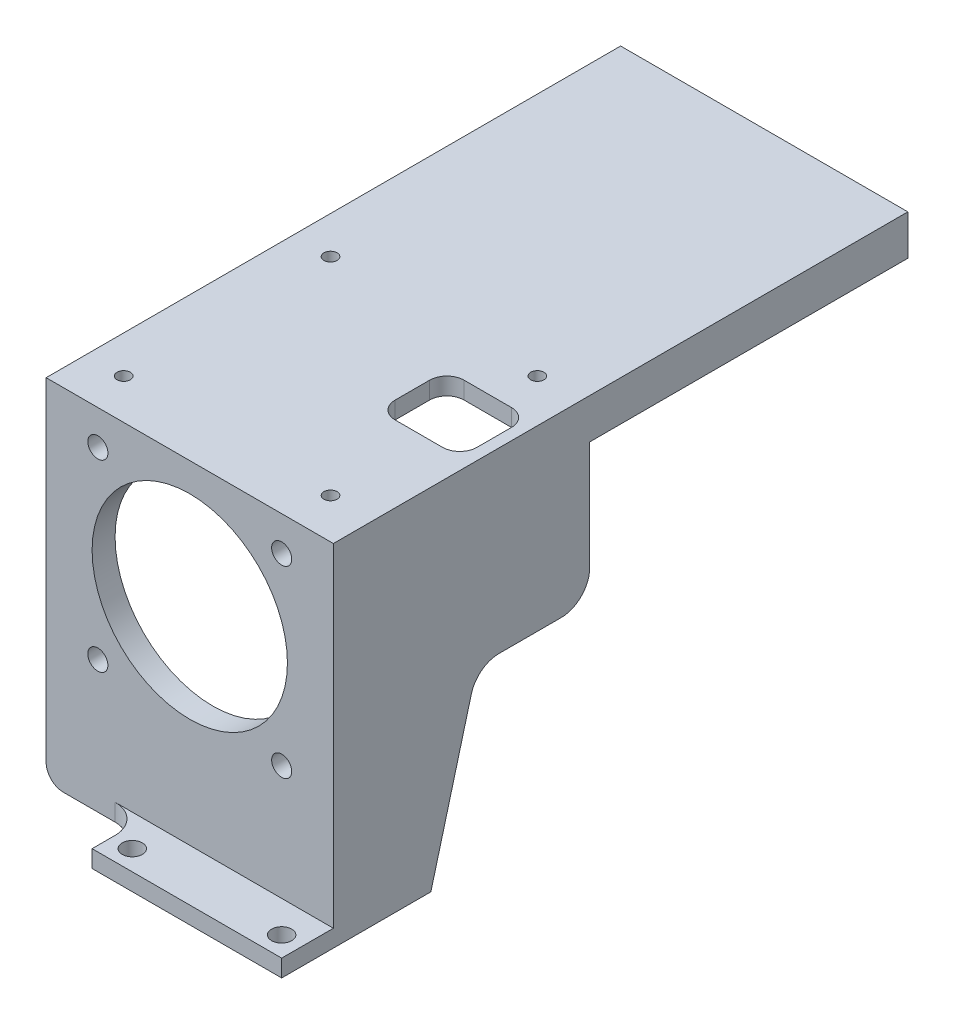
SolidWorks part; units mm, degrees
ref_plane "前视基准面" through (0, 0, 0) normal (0, 0, 1) x (1, 0, 0)
ref_plane "上视基准面" through (0, 0, 0) normal (0, 1, 0) x (1, 0, 0)
ref_plane "右视基准面" through (0, 0, 0) normal (1, 0, 0) x (0, 0, -1)
sketch "草图1" plane through (0, 0, 0) normal (0, 1, 0) x (1, 0, 0)
  line L1 (-16.5, -5) -> (16.5, -5)
  line L2 (-16.5, -5) -> (-16.5, 5)
  line L3 (-16.5, 5) -> (16.5, 5)
  line L4 (16.5, -5) -> (16.5, 5)
  line L5 (-16.5, -5) -> (16.5, 5) construction
  line L6 (-16.5, 5) -> (16.5, -5) construction
  point P0 (0, 0)
  dimension "D1" = 33
  dimension "D2" = 10
extrude "凸台-拉伸1" add sketch "草图1" along normal blind 3
sketch "草图2" plane through (0, 3, 0) normal (0, 1, 0) x (1, 0, 0)
  line L0 (16.5, -5) -> (16.5, 5) construction
  line L1 (-16.5, -5) -> (16.5, -5) construction
  line L2 (-16.5, 5) -> (-16.5, -5) construction
  point P0 (-13, -1.5)
  point P1 (13, -1.5)
  dimension "D1" = 3.5
  dimension "D2" = 3.5
  dimension "D3" = 3.5
  dimension "D4" = 3.5
sketch "草图3" plane through (0, 3, 0) normal (0, 1, 0) x (1, 0, 0)
  point P0 (-13, -1.5)
  point P3 (13, -1.5)
hole_wizard "孔1" positions "草图3" profile "草图4" legacy end condition through all
sketch "草图4" plane through (-13, 3, 1.5) normal (1, 0, 0) x (0, 0, 1)
  line L0 (0, 0) -> (0, 3)
  line L1 (0, 3) -> (1.75, 3)
  line L2 (1.75, 3) -> (1.75, 0)
  line L3 (1.75, 0) -> (0, 0)
  line L4 (0, 110) -> (0, -10) construction
  dimension "直径" = 3.5
  dimension "深度" = 3
sketch "草图5" plane through (0, 0, 0) normal (0, -1, 0) x (1, 0, 0)
  line L1 (-16.5, -5) -> (16.5, -5)
  line L2 (-16.5, -5) -> (-16.5, -8)
  line L3 (-16.5, -8) -> (16.5, -8)
  line L4 (16.5, -5) -> (16.5, -8)
  dimension "D1" = 33
  dimension "D2" = 3
extrude "凸台-拉伸2" add sketch "草图5" against normal blind 3
sketch "草图6" plane through (0, 3, 0) normal (0, 1, 0) x (1, 0, 0)
  line L0 (16.5, -5) -> (16.5, 8) construction
  line L1 (-16.5, 8) -> (16.5, 8)
  line L2 (-16.5, 8) -> (-16.5, 4)
  line L3 (-16.5, 4) -> (16.5, 4)
  line L4 (16.5, 8) -> (16.5, 4)
  dimension "D1" = 4
extrude "凸台-拉伸3" add sketch "草图6" along normal blind 55
sketch "草图7" plane through (0, 58, 0) normal (0, 1, 0) x (1, 0, 0)
  line L1 (16.5, 4) -> (-33.5, 4)
  line L2 (16.5, 4) -> (16.5, 8)
  line L3 (16.5, 8) -> (-33.5, 8)
  line L4 (-33.5, 4) -> (-33.5, 8)
  dimension "D1" = 50
  dimension "D2" = 4
extrude "凸台-拉伸4" add sketch "草图7" along normal blind 3
sketch "草图8" plane through (0, 0, -8) normal (0, 0, -1) x (-1, 0, 0)
  line L1 (33.5, 58) -> (-16.5, 58)
  line L2 (33.5, 58) -> (33.5, 61)
  line L3 (33.5, 61) -> (-16.5, 61)
  line L4 (-16.5, 58) -> (-16.5, 61)
extrude "凸台-拉伸5" add sketch "草图8" along normal blind 56
sketch "草图12" plane through (0, 61, 0) normal (0, 1, 0) x (1, 0, 0)
  line L0 (-33.5, 4) -> (16.5, 4) construction
  line L1 (16.5, 4) -> (16.5, 64) construction
  line L2 (12.25, 34) -> (12.25, 54)
  point P0 (12.25, 34)
  dimension "D1" = 30
  dimension "D2" = 4.25
  dimension "D3" = 20
sketch "草图15" plane through (16.5, 0, 0) normal (1, 0, 0) x (0, 0, -1)
  line L0 (8, 0) -> (48.612, 58)
  line L1 (64, 58) -> (8, 58) construction
  line L2 (8, 8.7172) -> (42.5082, 58)
  line L3 (8, 58) -> (8, 0) construction
  line L4 (8, 8.7172) -> (8, 0)
  line L5 (42.5082, 58) -> (48.612, 58)
  dimension "D1" = 55
  dimension "D2" = 5
extrude "凸台-拉伸6" add sketch "草图15" against normal blind 5
sketch "草图16" plane through (0, 0, -4) normal (0, 0, 1) x (1, 0, 0)
  line L0 (-16.5, 0) -> (-33.5, 58)
  line L1 (-28.2897, 58) -> (-16.5, 17.7765)
  line L2 (-33.5, 58) -> (-16.5, 58) construction
  line L3 (-16.5, 58) -> (-16.5, 3) construction
  line L4 (-33.5, 58) -> (-28.2897, 58)
  line L5 (-16.5, 17.7765) -> (-16.5, 0)
  dimension "D1" = 5
extrude "凸台-拉伸7" add sketch "草图16" against normal blind 4
sketch "草图20" plane through (0, 0, -64) normal (0, 0, -1) x (-1, 0, 0)
  line L1 (-16.5, 61) -> (33.5, 61)
  line L2 (-16.5, 61) -> (-16.5, 58)
  line L3 (-16.5, 58) -> (33.5, 58)
  line L4 (33.5, 61) -> (33.5, 58)
extrude "凸台-拉伸9" add sketch "草图20" along normal blind 40
sketch "草图33" plane through (0, 0, -4) normal (0, 0, 1) x (1, 0, 0)
  line L0 (-28.2897, 58) -> (-16.5, 17.7765)
  line L1 (-16.5, 17.7765) -> (-16.5, 58)
  line L2 (-16.5, 58) -> (-28.2897, 58)
extrude "凸台-拉伸15" add sketch "草图33" against normal blind 4
sketch "草图32" plane through (0, 58, 0) normal (0, -1, 0) x (1, 0, 0)
  line L0 (-27.5, -8) -> (-27.5, -63)
  line L1 (-33.5, -8) -> (-16.5, -8) construction
  line L2 (-27.5, -63) -> (-24.5, -63)
  line L3 (-27.5, -63) -> (-27.5, -8)
  line L4 (-27.5, -8) -> (-24.5, -8)
  line L5 (-24.5, -63) -> (-24.5, -8)
  line L6 (-33.5, -104) -> (-33.5, -8) construction
  dimension "D1" = 55
  dimension "D2" = 3
  dimension "D3" = 6
sketch "草图34" plane through (0, 0, -4) normal (0, 0, 1) x (1, 0, 0)
  line L0 (-33.5, 58) -> (-33.5, 0)
  line L1 (-33.5, 0) -> (-16.5, 0)
  line L2 (-16.5, 0) -> (-33.5, 58)
extrude "凸台-拉伸16" add sketch "草图34" against normal blind 4
fillet "圆角1" radius 3 1 edges at (-33.5, 0, -6)
sketch "草图35" plane through (0, 0, -4) normal (0, 0, 1) x (1, 0, 0)
  line L0 (-33.5, 3) -> (16.5, 58)
  line L2 (16.5, 3) -> (-33.5, 3)
  line L3 (16.5, 3) -> (16.5, 58)
  line L4 (16.5, 58) -> (-33.5, 58)
  line L5 (-33.5, 3) -> (-33.5, 58)
  line L6 (-24.5, 23) -> (7.5, 23)
  line L7 (-24.5, 23) -> (-24.5, 55)
  line L8 (-24.5, 55) -> (7.5, 55)
  line L9 (7.5, 23) -> (7.5, 55)
  line L10 (-24.5, 23) -> (7.5, 55) construction
  line L11 (-24.5, 55) -> (7.5, 23) construction
  point P4 (-8.5, 39)
  dimension "D1" = 32
  dimension "D2" = 32
  dimension "D3" = 25
  dimension "D4" = 19
sketch "草图36" plane through (0, 0, -4) normal (0, 0, 1) x (1, 0, 0)
  point P0 (-24.5, 55)
  point P3 (-24.5, 23)
  point P6 (7.5, 23)
  point P9 (7.5, 55)
hole_wizard "孔5" positions "草图36" profile "草图37" legacy end condition up to next
sketch "草图37" plane through (-24.5, 55, -4) normal (1, 0, 0) x (0, -1, 0)
  line L0 (0, 0) -> (0, 4)
  line L1 (0, 4) -> (1.75, 4)
  line L2 (1.75, 4) -> (1.75, 0)
  line L3 (1.75, 0) -> (0, 0)
  line L4 (0, 110) -> (0, -10) construction
  dimension "直径" = 3.5
  dimension "深度" = 4
sketch "草图38" plane through (0, 0, -4) normal (0, 0, 1) x (1, 0, 0)
  point P0 (-8.5, 39)
hole_wizard "孔6" positions "草图38" profile "草图39" legacy end condition up to next
sketch "草图39" plane through (-8.5, 39, -4) normal (1, 0, 0) x (0, -1, 0)
  line L0 (0, 0) -> (0, 4)
  line L1 (0, 4) -> (17, 4)
  line L2 (17, 4) -> (17, 0)
  line L3 (17, 0) -> (0, 0)
  line L4 (0, 110) -> (0, -10) construction
  dimension "直径" = 34
  dimension "深度" = 4
sketch "草图40" plane through (0, 58, 0) normal (0, -1, 0) x (1, 0, 0)
  line L0 (11.5, -29) -> (-44.5, -29)
  line L1 (11.5, -8) -> (-44.5, -8)
  line L2 (11.5, -8) -> (11.5, -50)
  line L3 (11.5, -50) -> (-44.5, -50)
  line L4 (-44.5, -8) -> (-44.5, -50)
  line L6 (-27, -47) -> (9, -47)
  line L7 (-27, -47) -> (-27, -11)
  line L8 (-27, -11) -> (9, -11)
  line L9 (9, -47) -> (9, -11)
  line L10 (-27, -47) -> (9, -11) construction
  line L11 (-27, -11) -> (9, -47) construction
  point P7 (-9, -29)
  dimension "D1" = 42
  dimension "D2" = 56
  dimension "D3" = 36
  dimension "D4" = 36
  dimension "D5" = 2.5
sketch "草图41" plane through (0, 58, 0) normal (0, -1, 0) x (-1, 0, 0)
  point P0 (-9, 11)
  point P3 (-9, 47)
  point P6 (27, 47)
  point P9 (27, 11)
hole_wizard "孔7" positions "草图41" profile "草图42" legacy end condition up to next
sketch "草图42" plane through (9, 58, -11) normal (1, 0, 0) x (0, 0, -1)
  line L0 (0, 0) -> (0, 3)
  line L1 (0, 3) -> (1.15, 3)
  line L2 (1.15, 3) -> (1.15, 0)
  line L3 (1.15, 0) -> (0, 0)
  line L4 (0, 110) -> (0, -10) construction
  dimension "直径" = 2.3
  dimension "深度" = 3
sketch "草图48" plane through (16.5, 0, 0) normal (1, 0, 0) x (0, 0, -1)
  line L0 (8, 8.7172) -> (8, 58)
  line L1 (8, 58) -> (42.5082, 58)
  line L2 (42.5082, 58) -> (8, 8.7172)
extrude "凸台-拉伸17" add sketch "草图48" against normal blind 5
sketch "草图49" plane through (16.5, 0, 0) normal (1, 0, 0) x (0, 0, -1)
  line L0 (4, 23) -> (4, 55) construction
  line L1 (48.612, 58) -> (4, 58)
  line L2 (48.612, 58) -> (48.612, 30)
  line L3 (48.612, 30) -> (4, 30)
  line L4 (4, 58) -> (4, 30)
  dimension "D1" = 28
extrude "凸台-拉伸18" add sketch "草图49" against normal blind 5
sketch "草图50" plane through (0, 61, 0) normal (0, 1, 0) x (1, 0, 0)
  line L0 (-33.5, 104) -> (16.5, 104) construction
  line L1 (6.25, 40) -> (18.25, 40)
  line L2 (6.25, 40) -> (6.25, 28)
  line L3 (6.25, 28) -> (18.25, 28)
  line L4 (18.25, 40) -> (18.25, 28)
  line L5 (6.25, 40) -> (18.25, 28) construction
  line L6 (6.25, 28) -> (18.25, 40) construction
  line L7 (12.25, 40) -> (0.25, 40)
  line L8 (12.25, 40) -> (12.25, 28)
  line L9 (12.25, 28) -> (0.25, 28)
  line L10 (0.25, 40) -> (0.25, 28)
  line L11 (16.5, 4) -> (16.5, 104) construction
  line L12 (11.5, 40) -> (11.5, 28)
  line L13 (11.5, 8) -> (11.5, 50) construction
  point P0 (12.25, 34)
  dimension "D1" = 12
  dimension "D2" = 12
  dimension "D3" = 12
  dimension "D4" = 12
  dimension "D5" = 70
  dimension "D6" = 4.25
extrude "切除-拉伸1" cut sketch "草图50" against normal blind 10
sketch "草图51" plane through (16.5, 0, 0) normal (1, 0, 0) x (0, 0, -1)
  line L0 (29.0062, 30) -> (20.9678, 0)
  line L1 (20.9678, 0) -> (8, 0)
  line L2 (8, 0) -> (29.0062, 30)
  dimension "D1" = 20
extrude "凸台-拉伸19" add sketch "草图51" against normal blind 5
fillet "圆角2" radius 5 2 edges at (14, 30, -48.612) (14, 30, -29.0062)
sketch "草图52" plane through (0, 61, 0) normal (0, 1, 0) x (1, 0, 0)
  line L1 (11.5, 40) -> (14.5, 40)
  line L2 (11.5, 40) -> (11.5, 28)
  line L3 (11.5, 28) -> (14.5, 28)
  line L4 (14.5, 40) -> (14.5, 28)
  dimension "D1" = 12
  dimension "D2" = 3
extrude "切除-拉伸2" cut sketch "草图52" against normal through all
fillet "圆角3" radius 3 4 edges at (0.25, 59.5, -28) (0.25, 59.5, -40) (14.5, 45.5, -40) (14.5, 43.6224, -28)
fillet "圆角4" radius 5 1 edges at (-16.5, 1.5, -4)
sketch "草图53" plane through (0, 58, 0) normal (0, -1, 0) x (1, 0, 0)
  line L0 (-33.5, -104) -> (-33.5, -8) construction
  line L1 (11.5, -48.612) -> (16.5, -48.612)
  line L2 (11.5, -48.612) -> (11.5, -104)
  line L3 (11.5, -104) -> (16.5, -104)
  line L4 (16.5, -48.612) -> (16.5, -104)
  line L5 (-33.5, -59) -> (-28.5, -59)
  line L6 (-33.5, -59) -> (-33.5, -104)
  line L7 (-33.5, -104) -> (-28.5, -104)
  line L8 (-28.5, -59) -> (-28.5, -104)
  line L9 (16.5, -104) -> (-33.5, -104) construction
  dimension "D1" = 45
  dimension "D2" = 5
extrude "凸台-拉伸20" add sketch "草图53" along normal blind 4
